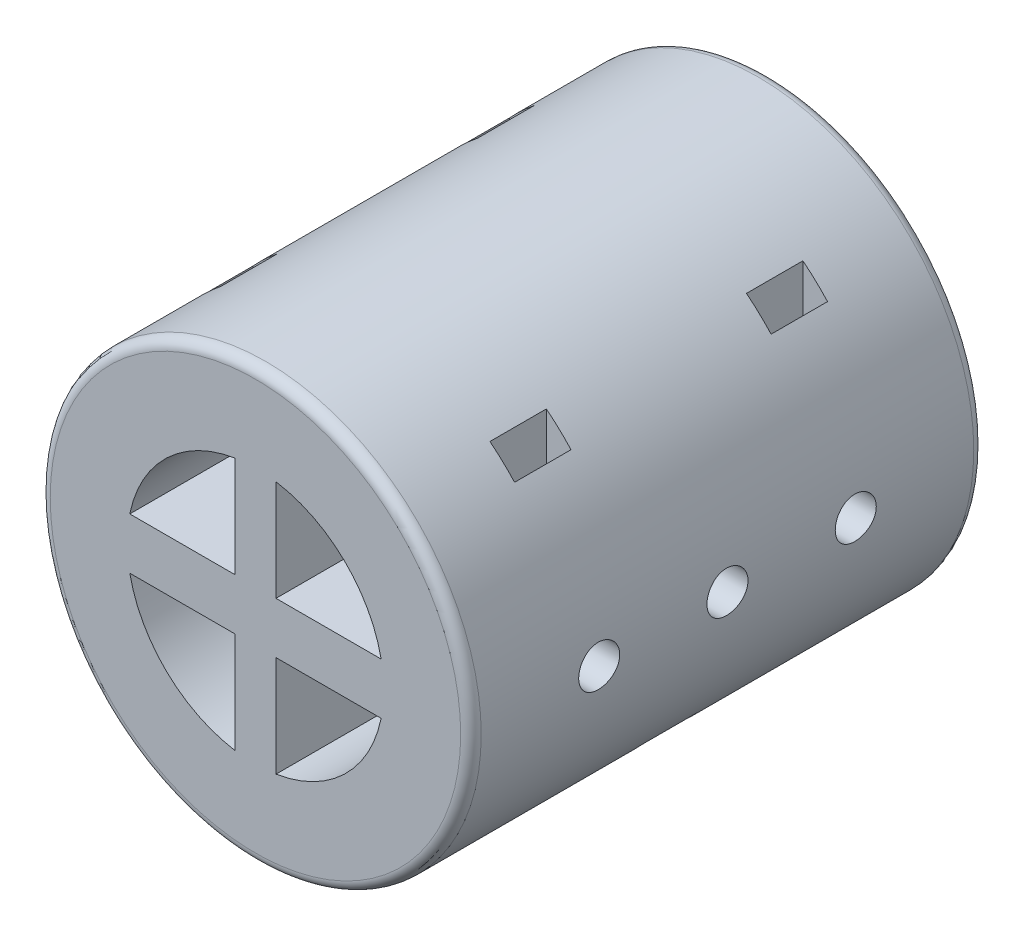
SolidWorks part; units mm, degrees
material "ABS"
ref_plane "Спереди" through (0, 0, 0) normal (0, 0, 1) x (1, 0, 0)
ref_plane "Сверху" through (0, 0, 0) normal (0, 1, 0) x (1, 0, 0)
ref_plane "Справа" through (0, 0, 0) normal (1, 0, 0) x (0, 0, -1)
other "Configuration Table"
sketch "Эскиз1" plane through (0, 0, 0) normal (0, 0, 1) x (1, 0, 0)
  circle A0 centre (0, 0) radius 21
  dimension "D1" = 42
extrude "Бобышка-Вытянуть1" add sketch "Эскиз1" along normal blind 50
fillet "Скругление1" radius 1 1 edges at (21, 0, 50)
fillet "Скругление2" radius 1 1 edges at (21, 0, 0)
ref_plane "Плоскость1" through (21, 0, 0) normal (1, 0, 0) x (0, 0, -1)
sketch "Эскиз2" plane through (21, 0, 0) normal (1, 0, 0) x (0, 0, -1)
  line L0 (-50, 20) -> (-50, -20) construction
  line L1 (-49, -21) -> (-1, -21) construction
  circle A0 centre (-37.5, 0) radius 2
  circle A1 centre (-25, 0) radius 2
  circle A2 centre (-12.5, 0) radius 2
  dimension "D1" = 4
  dimension "D2" = 4
  dimension "D3" = 4
  dimension "D4" = 12.5
  dimension "D5" = 12.5
  dimension "D6" = 12.5
  dimension "D7" = 21
  dimension "D8" = 21
  dimension "D9" = 21
extrude "Вырез-Вытянуть1" cut sketch "Эскиз2" against normal through all contours A0 | A1 | A2
sketch "Эскиз3" plane through (21, 0, 0) normal (1, 0, 0) x (0, 0, -1)
  line L0 (-50, 20) -> (-50, -20) construction
  line L8 (-25, 3.1754) -> (-27.75, 1.5877)
  line L9 (-37.5, 3.1754) -> (-40.25, 1.5877)
  line L10 (-40.25, 1.5877) -> (-40.25, -1.5877)
  line L11 (-40.25, -1.5877) -> (-37.5, -3.1754)
  line L12 (-37.5, -3.1754) -> (-34.75, -1.5877)
  line L13 (-34.75, -1.5877) -> (-34.75, 1.5877)
  line L14 (-34.75, 1.5877) -> (-37.5, 3.1754)
  line L15 (-27.75, 1.5877) -> (-27.75, -1.5877)
  line L16 (-27.75, -1.5877) -> (-25, -3.1754)
  line L17 (-25, -3.1754) -> (-22.25, -1.5877)
  line L18 (-22.25, -1.5877) -> (-22.25, 1.5877)
  line L19 (-22.25, 1.5877) -> (-25, 3.1754)
  line L20 (-12.5, 3.1754) -> (-15.25, 1.5877)
  line L21 (-15.25, 1.5877) -> (-15.25, -1.5877)
  line L22 (-15.25, -1.5877) -> (-12.5, -3.1754)
  line L23 (-12.5, -3.1754) -> (-9.75, -1.5877)
  line L24 (-9.75, -1.5877) -> (-9.75, 1.5877)
  line L25 (-9.75, 1.5877) -> (-12.5, 3.1754)
  circle A0 centre (-37.5, 0) radius 2.75 construction
  circle A1 centre (-25, 0) radius 2.75 construction
  circle A2 centre (-12.5, 0) radius 2.75 construction
  dimension "D4" = 5.5
  dimension "D5" = 5.5
  dimension "D6" = 5.5
  dimension "D7" = 12.5
  dimension "D8" = 12.5
  dimension "D9" = 12.5
extrude "Вырез-Вытянуть2" cut sketch "Эскиз3" against normal blind 2.4 from offset 5 offset against normal yes
mirror "Зеркальное отражение1" about plane through (0, 0, 0) normal (1, 0, 0) of "Вырез-Вытянуть2"
sketch "Эскиз4" plane through (0, 0, 50) normal (0, 0, 1) x (1, 0, 0)
  line L0 (0, 0) -> (-12.5, 0) construction
  line L1 (0, 0) -> (12.5, 0) construction
  line L2 (0, 0) -> (0, 12.5) construction
  line L3 (0, 0) -> (0, -12.5) construction
  line L4 (2, 2.5) -> (2, 12.339)
  line L5 (-2, 2.5) -> (-2, 12.339)
  line L6 (-2, -2.5) -> (-2, -12.339)
  line L7 (2, -2.5) -> (2, -12.339)
  line L8 (-12.2474, 2.5) -> (-2, 2.5)
  line L9 (-12.2474, -2.5) -> (-2, -2.5)
  line L10 (2, 2.5) -> (12.2474, 2.5)
  line L11 (2, -2.5) -> (12.2474, -2.5)
  circle A0 centre (0, 0) radius 12.5
  circle A5 centre (0, 0) radius 20 construction
  dimension "D1" = 25
  dimension "D3" = 2.5
  dimension "D4" = 2.5
  dimension "D2" = 2
  dimension "D5" = 2
  dimension "D6" = 2
  dimension "D7" = 2
extrude "Вырез-Вытянуть9" cut sketch "Эскиз4" against normal through all contours L5 A0 L8 | L10 A0 L4 | L7 A0 L11 | L9 A0 L6 region at (6.1084, 6.4596, 50) region at (-6.1084, 6.4596, 50) region at (6.1084, -6.4596, 50) region at (-6.1084, -6.4596, 50)
ref_plane "Плоскость2" through (0, 21, 0) normal (0, 1, 0) x (1, 0, 0)
sketch "Эскиз6" plane through (0, 21, 0) normal (0, 1, 0) x (1, 0, 0)
  line L1 (13.1, -34.75) -> (15.5, -34.75)
  line L2 (13.1, -34.75) -> (13.1, -40.25)
  line L3 (13.1, -40.25) -> (15.5, -40.25)
  line L4 (15.5, -34.75) -> (15.5, -40.25)
  line L5 (13.1, -34.75) -> (15.5, -40.25) construction
  line L6 (13.1, -40.25) -> (15.5, -34.75) construction
  line L8 (21, -49) -> (21, -39.5) construction
  line L9 (-20, -50) -> (20, -50) construction
  line L16 (13.1, -22.25) -> (15.5, -22.25)
  line L17 (15.5, -22.25) -> (15.5, -27.75)
  line L18 (13.1, -22.25) -> (13.1, -27.75)
  line L19 (13.1, -27.75) -> (15.5, -27.75)
  line L20 (13.1, -9.75) -> (15.5, -9.75)
  line L21 (15.5, -9.75) -> (15.5, -15.25)
  line L22 (13.1, -9.75) -> (13.1, -15.25)
  line L23 (13.1, -15.25) -> (15.5, -15.25)
  line L24 (13.1, -34.75) -> (13.1, -22.25) construction
  point P0 (14.3, -37.5)
  dimension "D1" = 2.4
  dimension "D2" = 5.5
  dimension "D3" = 5.5
  dimension "D4" = 9.75
  dimension "D6" = 12.5
  dimension "D5" = 3
extrude "Вырез-Вытянуть10" cut sketch "Эскиз6" against normal blind 21 contours L4 L3 L2 L1 | L21 L23 L22 L20
extrude "Вырез-Вытянуть11" cut sketch "Эскиз6<5>" against normal blind 21 from offset 21 contours L17 L19 L18 L16 offset against normal yes
sketch "Эскиз6<5>" plane through (0, 21, 0) normal (0, 1, 0) x (1, 0, 0) same geometry as "Эскиз6"
mirror "Зеркальное отражение2" about plane through (0, 0, 0) normal (1, 0, 0) of "Вырез-Вытянуть10", "Вырез-Вытянуть11"
equation "\"D4@Эскиз4\"=\"D3@Эскиз4\""
equation "\"D5@Эскиз4\"=\"D2@Эскиз4\""
equation "\"D6@Эскиз4\"=\"D2@Эскиз4\""
equation "\"D7@Эскиз4\"=\"D2@Эскиз4\""
equation "\"D8@Эскиз2\"=\"D7@Эскиз2\""
equation "\"D9@Эскиз2\"=\"D7@Эскиз2\""
